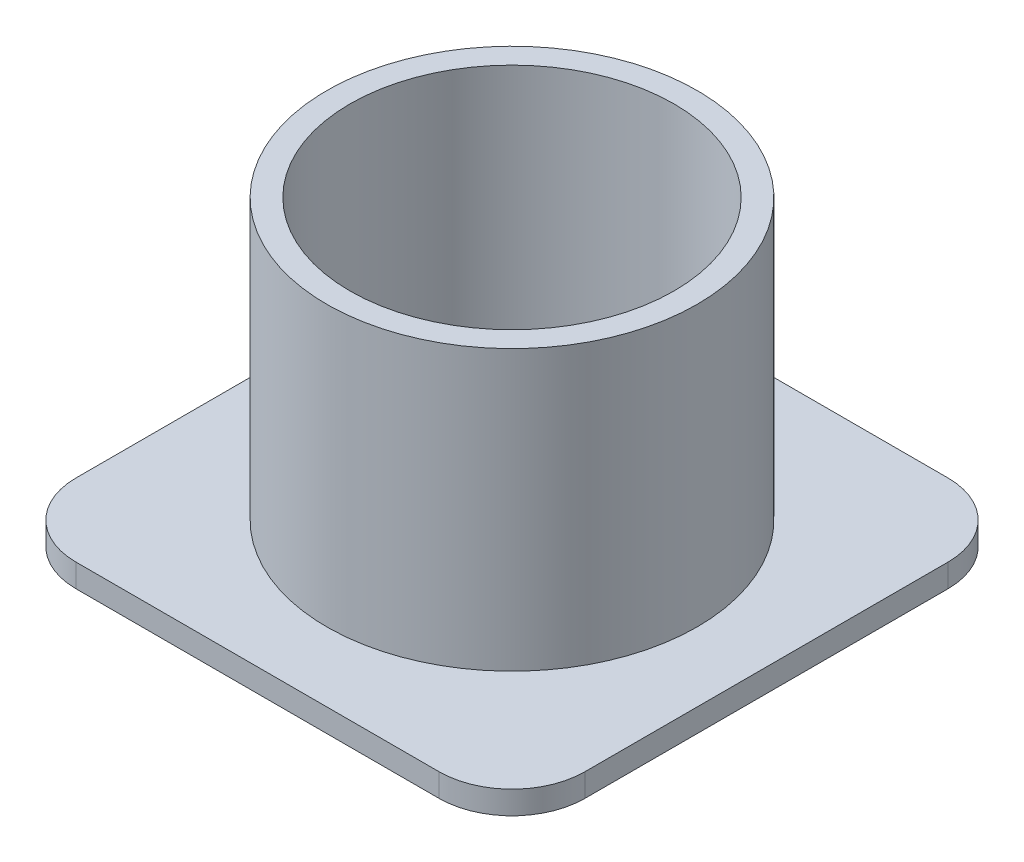
SolidWorks part; units mm, degrees
material "Acrylic (Medium-high impact)"
ref_plane "Front Plane" through (0, 0, 0) normal (0, 0, 1) x (1, 0, 0)
ref_plane "Top Plane" through (0, 0, 0) normal (0, 1, 0) x (1, 0, 0)
ref_plane "Right Plane" through (0, 0, 0) normal (1, 0, 0) x (0, 0, -1)
ref_axis "Axis1" through (0, -55, 0) along (0, 1, 0)
sketch "Sketch1" plane through (0, 0, 0) normal (0, 1, 0) x (1, 0, 0)
  line L1 (-24.925, 34.925) -> (24.925, 34.925)
  line L2 (-34.925, 24.925) -> (-34.925, -24.925)
  line L3 (-24.925, -34.925) -> (24.925, -34.925)
  line L4 (34.925, 24.925) -> (34.925, -24.925)
  line L5 (-34.925, 34.925) -> (34.925, -34.925) construction
  line L6 (-34.925, -34.925) -> (34.925, 34.925) construction
  arc A0 (-34.925, -24.925) -> (-24.925, -34.925) centre (-24.925, -24.925) ccw
  arc A1 (24.925, -34.925) -> (34.925, -24.925) centre (24.925, -24.925) ccw
  arc A2 (24.925, 34.925) -> (34.925, 24.925) centre (24.925, 24.925) cw
  arc A3 (-24.925, 34.925) -> (-34.925, 24.925) centre (-24.925, 24.925) ccw
  point P0 (0, 0)
  dimension "D1" = 10
  dimension "D2" = 69.85
  dimension "D3" = 69.85
extrude "Boss-Extrude1" add sketch "Sketch1" along normal blind 3.175
sketch "Sketch2" plane through (0, 3.175, 0) normal (0, 1, 0) x (1, 0, 0)
  circle A0 centre (0, 0) radius 22.2451
extrude "Cut-Extrude1" cut sketch "Sketch2" against normal blind 6.35
extrude "Extrude-Thin1" add sketch "Sketch2<2>" along normal blind 38.35 thin thin type one direction wall 3.175
sketch "Sketch2<2>" plane through (0, 3.175, 0) normal (0, 1, 0) x (1, 0, 0) same geometry as "Sketch2"
